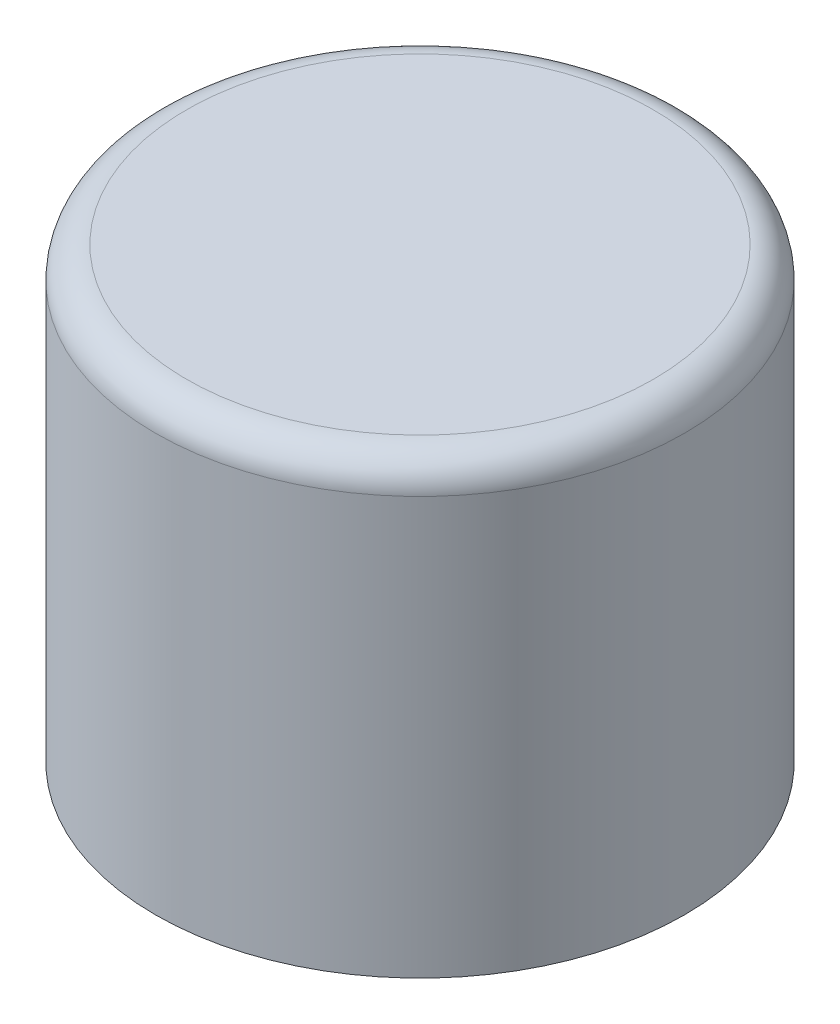
SolidWorks part; units mm, degrees
ref_plane "Plan de face" through (0, 0, 0) normal (0, 0, 1) x (1, 0, 0)
ref_plane "Plan de dessus" through (0, 0, 0) normal (0, 1, 0) x (1, 0, 0)
ref_plane "Plan de droite" through (0, 0, 0) normal (1, 0, 0) x (0, 0, -1)
sketch "Esquisse1" plane through (0, 0, 0) normal (0, 0, 1) x (1, 0, 0)
  line L0 (0, 0) -> (0, 28.8) construction
  line L2 (-17, 0) -> (-17, 28.8)
  line L3 (-17, 28.8) -> (0, 28.8)
  line L4 (0, 28.8) -> (0, 25.8)
  line L5 (0, 25.8) -> (-12.5, 25.8) construction
  line L6 (-12.5, 25.8) -> (-12.5, 2) construction
  line L7 (-12.5, 2) -> (-12, 2)
  line L8 (-12, 2) -> (-12, 0)
  line L17 (-12, 0) -> (-17, 0)
  line L18 (-12.5, 2) -> (-12.5, 3)
  line L19 (-12.5, 3) -> (-12, 3)
  line L20 (-12, 3) -> (-12, 25.8)
  line L21 (-12, 25.8) -> (0, 25.8)
  dimension "D1" = 2
  dimension "D3" = 17
  dimension "D4" = 1
  dimension "D5" = 0.5
  dimension "D6" = 12
  dimension "D7" = 25.8
  dimension "D9" = 3
revolve "Révolution1" add sketch "Esquisse1" angle 360 about L0
fillet "Congé1" radius 2 1 edges at (17, 28.8, 0)
